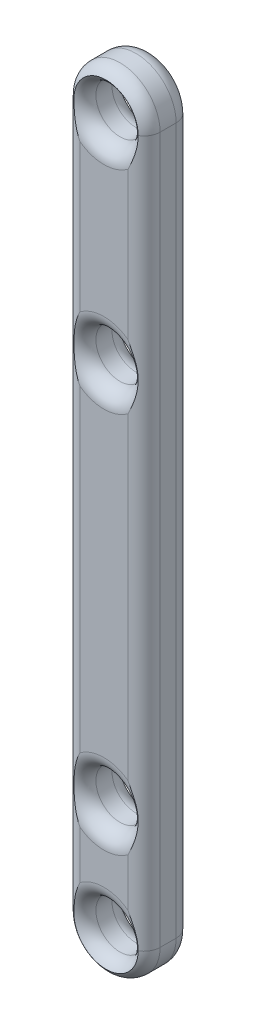
SolidWorks part; units mm, degrees
ref_plane "Front Plane" through (0, 0, 0) normal (0, 0, 1) x (1, 0, 0)
ref_plane "Top Plane" through (0, 0, 0) normal (0, 1, 0) x (1, 0, 0)
ref_plane "Right Plane" through (0, 0, 0) normal (1, 0, 0) x (0, 0, -1)
sketch "Sketch1" plane through (0, 0, 0) normal (0, 0, 1) x (1, 0, 0)
  line L0 (0, 0) -> (0, -44) construction
  line L1 (2.5, 0) -> (2.5, -44)
  line L2 (-2.5, 0) -> (-2.5, -44)
  arc A0 (2.5, 0) -> (-2.5, 0) centre (0, 0) ccw
  arc A1 (-2.5, -44) -> (2.5, -44) centre (0, -44) ccw
  circle A2 centre (0, 0) radius 1.5
  circle A3 centre (0, -13.2) radius 1.5
  circle A4 centre (0, -37) radius 1.5
  circle A5 centre (0, -44) radius 1.5
  point P3 (0, -22)
  dimension "D3" = 3
  dimension "D4" = 3
  dimension "D5" = 3
  dimension "D6" = 3
  dimension "D1" = 44
  dimension "D2" = 5
  dimension "D7" = 13.2
  dimension "D8" = 37
extrude "Boss-Extrude1" add sketch "Sketch1" along normal blind 3
fillet "Fillet1" radius 1 16 edges at (0, 2.5, 3) (0, 2.5, 0) (-2.5, -22, 3) (-2.5, -22, 0) (0, -46.5, 3) (0, -46.5, 0) (2.5, -22, 3) (2.5, -22, 0) (1.5, 0, 0) (1.5, 0, 3) (1.5, -13.2, 0) (1.5, -13.2, 3) (1.5, -37, 0) (1.5, -37, 3) (1.5, -44, 0) (1.5, -44, 3)
